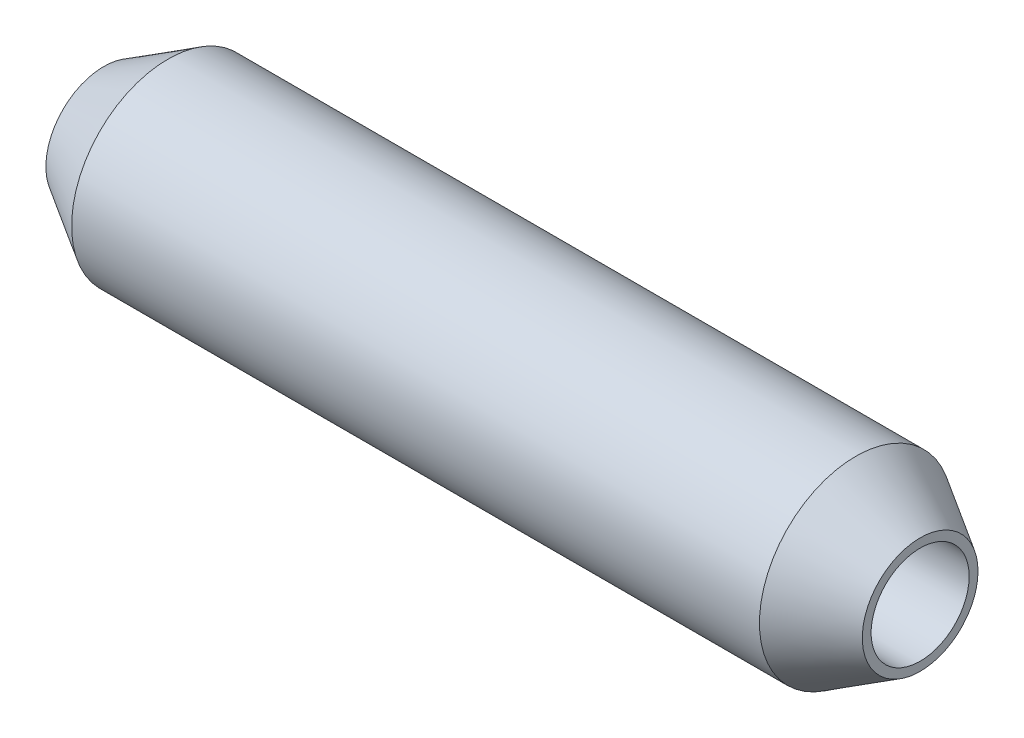
SolidWorks part; units mm, degrees
ref_plane "Front Plane" through (0, 0, 0) normal (0, 0, 1) x (1, 0, 0)
ref_plane "Top Plane" through (0, 0, 0) normal (0, 1, 0) x (1, 0, 0)
ref_plane "Right Plane" through (0, 0, 0) normal (1, 0, 0) x (0, 0, -1)
sketch "Sketch1" plane through (0, 0, 0) normal (1, 0, 0) x (0, 0, -1)
  circle A0 centre (0, 0) radius 3
  circle A1 centre (0, 0) radius 1.525
  dimension "D1" = 6
  dimension "D2" = 3.05
extrude "Boss-Extrude1" add sketch "Sketch1" along normal blind 25.4
chamfer "Chamfer1" distance 2 distance2 1.2 2 edges at (0, 0, -3) (25.4, 0, -3) first distance on face at (25.4, 0, -3)
